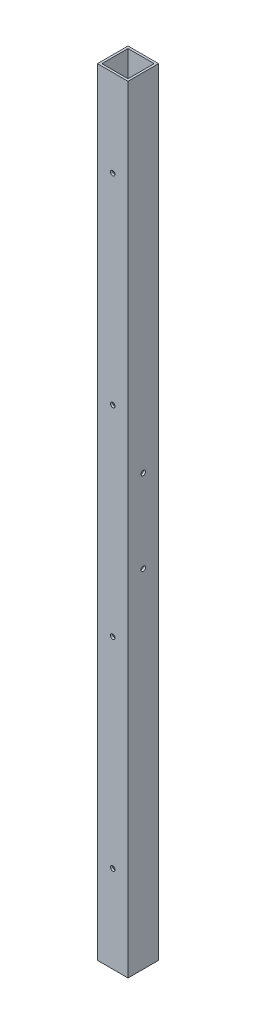
SolidWorks part; units mm, degrees
material "6061 Alloy"
ref_plane "Front Plane" through (0, 0, 0) normal (0, 0, 1) x (1, 0, 0)
ref_plane "Top Plane" through (0, 0, 0) normal (0, 1, 0) x (1, 0, 0)
ref_plane "Right Plane" through (0, 0, 0) normal (1, 0, 0) x (0, 0, -1)
sketch "Sketch1" plane through (0, 0, 0) normal (0, 1, 0) x (1, 0, 0)
  line L0 (-19.05, -19.05) -> (19.05, -19.05)
  line L1 (-22.225, -22.225) -> (22.225, -22.225)
  line L2 (-22.225, -22.225) -> (-22.225, 22.225)
  line L3 (-22.225, 22.225) -> (22.225, 22.225)
  line L4 (22.225, -22.225) -> (22.225, 22.225)
  line L5 (-22.225, -22.225) -> (22.225, 22.225) construction
  line L6 (-22.225, 22.225) -> (22.225, -22.225) construction
  line L7 (19.05, -19.05) -> (19.05, 19.05)
  line L8 (-19.05, 19.05) -> (19.05, 19.05)
  line L9 (-19.05, -19.05) -> (-19.05, 19.05)
  point P0 (0, 0)
  dimension "D1" = 44.45
  dimension "D2" = 3.175
extrude "Boss-Extrude1" add sketch "Sketch1" along normal blind 1130.3
hole_wizard "1/4 Clearance Hole1" positions "Sketch2" profile "Sketch3" hole size "1/4" standard "ANSI Inch" end condition through all
sketch "Sketch2" plane through (0, 0, 22.225) normal (0, 0, 1) x (1, 0, 0)
  line L0 (22.225, 565.15) -> (-22.225, 565.15) construction
  line L1 (22.225, 1130.3) -> (22.225, 0) construction
  line L2 (-22.225, 1130.3) -> (-22.225, 0) construction
  line L3 (22.225, 565.15) -> (22.225, 1130.3) construction
  line L4 (22.225, 847.725) -> (-22.225, 847.725) construction
  line L5 (-22.225, 0) -> (22.225, 0) construction
  line L6 (0, 1130.3) -> (0, 0) construction
  line L7 (-22.225, 1130.3) -> (22.225, 1130.3) construction
  point P15 (0, 1003.3)
  point P19 (0, 711.2)
  point P21 (0, 419.1)
  point P22 (0, 127)
  dimension "D1" = 127
  dimension "D2" = 292.1
  dimension "D3" = 292.1
sketch "Sketch3" plane through (0, 127, 22.225) normal (1, 0, 0) x (0, -1, 0)
  line L0 (0, 0) -> (0, 44.45)
  line L1 (0, 44.45) -> (3.3782, 44.45)
  line L2 (3.3782, 44.45) -> (3.3782, 0)
  line L5 (3.3782, 0) -> (0, 0)
  line L11 (0, -6.35) -> (0, 107.95) construction
  dimension "Thru Hole Dia." = 6.7564
  dimension "Thru Hole Depth" = 44.45
hole_wizard "1/4 Clearance Hole2" positions "Sketch4" profile "Sketch5" hole size "1/4" standard "ANSI Inch" end condition through all
sketch "Sketch4" plane through (22.225, 0, 0) normal (1, 0, 0) x (0, 0, -1)
  line L0 (22.225, 565.15) -> (-22.225, 565.15) construction
  line L1 (22.225, 1130.3) -> (22.225, 0) construction
  line L2 (-22.225, 1130.3) -> (-22.225, 0) construction
  line L3 (0, 1130.3) -> (0, 0) construction
  line L4 (-22.225, 1130.3) -> (22.225, 1130.3) construction
  point P0 (0, 625.475)
  point P2 (0, 504.825)
  dimension "D1" = 120.65
sketch "Sketch5" plane through (22.225, 625.475, 0) normal (0, 1, 0) x (0, 0, -1)
  line L0 (0, 0) -> (0, 44.45)
  line L1 (0, 44.45) -> (3.3782, 44.45)
  line L2 (3.3782, 44.45) -> (3.3782, 0)
  line L5 (3.3782, 0) -> (0, 0)
  line L11 (0, -6.35) -> (0, 107.95) construction
  dimension "Thru Hole Dia." = 6.7564
  dimension "Thru Hole Depth" = 44.45
